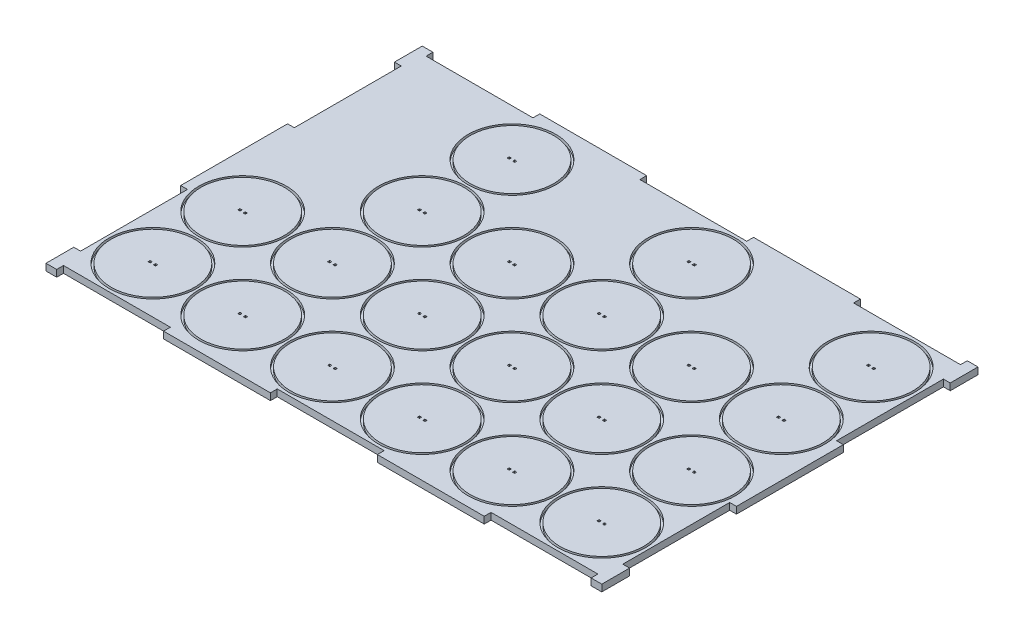
SolidWorks part; units mm, degrees
material "Oak"
ref_plane "Front Plane" through (0, 0, 0) normal (0, 0, 1) x (1, 0, 0)
ref_plane "Top Plane" through (0, 0, 0) normal (0, 1, 0) x (1, 0, 0)
ref_plane "Right Plane" through (0, 0, 0) normal (1, 0, 0) x (0, 0, -1)
sketch "Sketch2" plane through (0, 0, 0) normal (0, 1, 0) x (1, 0, 0)
  line L2 (105, -63) -> (63, -63) construction
  line L3 (105, -63) -> (-105, 63) construction
  line L4 (-105, -63) -> (-105, 63) construction
  line L5 (-105, 63) -> (105, 63) construction
  line L6 (-105, -63) -> (105, 63) construction
  circle A0 centre (105, -63) radius 20
  circle A1 centre (63, -63) radius 20
  circle A2 centre (21, -63) radius 20
  circle A3 centre (-21, -63) radius 20
  circle A4 centre (-63, -63) radius 20
  circle A5 centre (-105, -63) radius 20
  circle A6 centre (63, -21) radius 20
  circle A7 centre (21, -21) radius 20
  circle A8 centre (-21, -21) radius 20
  circle A9 centre (-63, -21) radius 20
  circle A10 centre (-105, -21) radius 20
  circle A11 centre (63, 21) radius 20
  circle A12 centre (21, 21) radius 20
  circle A13 centre (-21, 21) radius 20
  circle A14 centre (-63, 21) radius 20
  circle A17 centre (21, 63) radius 20
  circle A19 centre (-63, 63) radius 20
  circle A21 centre (105, -21) radius 20
  circle A22 centre (105, 21) radius 20
  circle A23 centre (105, 63) radius 20
  circle A24 centre (-105, 63) radius 20
  circle A25 centre (-105, 21) radius 20
  circle A26 centre (-21, 63) radius 20
  circle A27 centre (63, 63) radius 20
  point P0 (0, 0)
  dimension "D1" = 40
  dimension "D2" = 42
  dimension "D6" = 4
  dimension "D4" = 42
  dimension "D5" = 6
sketch "Sketch3" plane through (0, 0, 0) normal (0, 1, 0) x (1, 0, 0)
  line L1 (130, 88) -> (-130, 88)
  line L2 (130, 88) -> (130, -88)
  line L3 (130, -88) -> (-130, -88)
  line L4 (-130, 88) -> (-130, -88)
  line L5 (130, 88) -> (-130, -88) construction
  line L6 (130, -88) -> (-130, 88) construction
  circle A0 centre (-105, -63) radius 20 construction
  point P6 (0, 0)
  dimension "D1" = 25
  dimension "D2" = 25
extrude "Boss-Extrude2" add sketch "Sketch3" along normal mid plane 3.175
sketch "Sketch4" plane through (0, 1.5875, 0) normal (0, 1, 0) x (1, 0, 0)
  line L0 (105, -63) -> (63, -63) construction
  circle A25 centre (63, -63) radius 20.5
  circle A26 centre (105, -63) radius 20.5
  circle A27 centre (105, -63) radius 20.5
  circle A28 centre (105, -63) radius 19.5
  circle A29 centre (105, -63) radius 19.5
  circle A30 centre (63, -63) radius 19.5
  circle A31 centre (21, -63) radius 20.5
  circle A32 centre (21, -63) radius 19.5
  circle A33 centre (-21, -63) radius 20.5
  circle A34 centre (-21, -63) radius 19.5
  circle A35 centre (-63, -63) radius 20.5
  circle A36 centre (-63, -63) radius 19.5
  circle A37 centre (-105, -63) radius 20.5
  circle A38 centre (-105, -63) radius 19.5
  circle A39 centre (63, -21) radius 20.5
  circle A40 centre (63, -21) radius 19.5
  circle A41 centre (21, -21) radius 20.5
  circle A42 centre (21, -21) radius 19.5
  circle A43 centre (-21, -21) radius 20.5
  circle A44 centre (-21, -21) radius 19.5
  circle A45 centre (-63, -21) radius 20.5
  circle A46 centre (-63, -21) radius 19.5
  circle A47 centre (-105, -21) radius 20.5
  circle A48 centre (-105, -21) radius 19.5
  circle A49 centre (63, 21) radius 20.5
  circle A50 centre (63, 21) radius 19.5
  circle A51 centre (21, 21) radius 20.5
  circle A52 centre (21, 21) radius 19.5
  circle A53 centre (-21, 21) radius 20.5
  circle A54 centre (-21, 21) radius 19.5
  circle A55 centre (-63, 21) radius 20.5
  circle A56 centre (-63, 21) radius 19.5
  circle A61 centre (21, 63) radius 20.5
  circle A62 centre (21, 63) radius 19.5
  circle A65 centre (-63, 63) radius 20.5
  circle A66 centre (-63, 63) radius 19.5
  circle A69 centre (105, -21) radius 20.5
  circle A70 centre (105, -21) radius 19.5
  circle A71 centre (105, 21) radius 20.5
  circle A72 centre (105, 21) radius 19.5
  circle A73 centre (105, 63) radius 20.5
  circle A74 centre (105, 63) radius 19.5
  circle A75 centre (-105, 63) radius 20.5 [skipped]
  circle A76 centre (-105, 63) radius 19.5 [skipped]
  circle A77 centre (-105, 21) radius 19.5 [skipped]
  circle A78 centre (-105, 21) radius 20.5 [skipped]
  circle A79 centre (-21, 63) radius 20.5 [skipped]
  circle A80 centre (-21, 63) radius 19.5 [skipped]
  circle A81 centre (63, 63) radius 20.5 [skipped]
  circle A82 centre (63, 63) radius 19.5 [skipped]
  dimension "D3" = 42
  dimension "D1" = 0.5
  dimension "D2" = 0.5
  dimension "D4" = 6
  dimension "D5" = 4
extrude "Cut-Extrude1" cut sketch "Sketch4" against normal blind 1.5
sketch "Sketch5" plane through (0, 1.5875, 0) normal (0, 1, 0) x (1, 0, 0)
  line L0 (85, -63) -> (125, -63) construction
  line L1 (105, -58.1195) -> (105, -66.5107) construction
  line L2 (103.23, -62.5) -> (104.23, -62.5)
  line L3 (103.23, -62.5) -> (103.23, -63.5)
  line L4 (103.23, -63.5) -> (104.23, -63.5)
  line L5 (104.23, -62.5) -> (104.23, -63.5)
  line L6 (103.23, -62.5) -> (104.23, -63.5) construction
  line L7 (103.23, -63.5) -> (104.23, -62.5) construction
  line L8 (106.77, -63.5) -> (105.77, -62.5) construction
  line L9 (106.77, -62.5) -> (105.77, -63.5) construction
  line L10 (105.77, -62.5) -> (105.77, -63.5)
  line L11 (106.77, -63.5) -> (105.77, -63.5)
  line L12 (106.77, -62.5) -> (106.77, -63.5)
  line L13 (106.77, -62.5) -> (105.77, -62.5)
  circle A1 centre (-63, -63) radius 20
  circle A2 centre (-63, -63) radius 20
  circle A3 centre (-21, -63) radius 20
  circle A4 centre (-21, -63) radius 20
  circle A5 centre (21, -63) radius 20
  circle A6 centre (21, -63) radius 20
  circle A7 centre (63, -63) radius 20
  circle A8 centre (63, -63) radius 20
  circle A9 centre (105, -63) radius 20
  circle A10 centre (105, -63) radius 20
  circle A11 centre (21, 21) radius 20
  circle A12 centre (21, 21) radius 20
  circle A13 centre (63, 21) radius 20
  circle A14 centre (63, 21) radius 20
  circle A15 centre (-105, -21) radius 20
  circle A16 centre (-105, -21) radius 20
  circle A17 centre (-63, -21) radius 20
  circle A18 centre (-63, -21) radius 20
  circle A19 centre (-21, -21) radius 20
  circle A20 centre (-21, -21) radius 20
  circle A21 centre (21, -21) radius 20
  circle A22 centre (21, -21) radius 20
  circle A23 centre (63, -21) radius 20
  circle A24 centre (63, -21) radius 20
  circle A25 centre (-105, -63) radius 20
  circle A26 centre (-105, -63) radius 20
  circle A27 centre (-63, 63) radius 20
  circle A28 centre (-63, 63) radius 20
  circle A29 centre (21, 63) radius 20
  circle A30 centre (21, 63) radius 20
  circle A31 centre (-63, 21) radius 20
  circle A32 centre (-63, 21) radius 20
  circle A33 centre (-21, 21) radius 20
  circle A34 centre (-21, 21) radius 20
  circle A35 centre (105, 63) radius 20
  circle A36 centre (105, 63) radius 20
  circle A37 centre (105, 21) radius 20
  circle A38 centre (105, 21) radius 20
  circle A39 centre (105, -21) radius 20
  circle A40 centre (105, -21) radius 20
  point P62 (103.73, -63)
  point P73 (106.27, -63)
  dimension "D21" = 1.27
  dimension "D22" = 1
  dimension "D23" = 1
  dimension "D1" = 0
  dimension "D2" = 0
  dimension "D3" = 0
  dimension "D4" = 0
  dimension "D5" = 0
  dimension "D6" = 0
  dimension "D7" = 0
  dimension "D8" = 0
  dimension "D9" = 0
  dimension "D10" = 0
  dimension "D11" = 0
  dimension "D12" = 0
  dimension "D13" = 0
  dimension "D14" = 0
  dimension "D15" = 0
  dimension "D16" = 0
  dimension "D17" = 0
  dimension "D18" = 0
  dimension "D19" = 0
  dimension "D20" = 0
extrude "Cut-Extrude9" cut sketch "Sketch5" against normal blind 11.5 and the other way blind 11.5 contours L5 L2 L3 L4 | L12 L13 L10 L11 region at (103.73, 1.5875, 63) region at (106.27, 1.5875, 63)
pattern_linear "LPattern1" count 4 spacing 42 along (0, 0, -1) count 6 spacing 42 along (-1, 0, 0) skipping (2, 5), (3, 1), (3, 3), (3, 5) of "Cut-Extrude9"
sketch "Sketch9" plane through (0, 1.5875, 0) normal (0, 1, 0) x (1, 0, 0)
  line L0 (-130, 75) -> (-126.825, 75)
  line L1 (-130, 88) -> (-130, -88) construction
  line L2 (-126.825, 75) -> (-126.825, 25)
  line L3 (-130, -25) -> (-126.825, -25)
  line L4 (-126.825, -25) -> (-126.825, -75)
  line L5 (-126.825, -75) -> (-130, -75)
  line L6 (-130, 0) -> (130, 0) construction
  line L7 (-126.825, 25) -> (-130, 25)
  line L8 (130, 88) -> (-130, 88) construction
  line L9 (-130, -88) -> (130, -88) construction
  line L10 (0, 88) -> (0, -88) construction
  line L11 (126.825, 25) -> (130, 25)
  line L12 (126.825, -75) -> (130, -75)
  line L13 (126.825, -25) -> (126.825, -75)
  line L14 (130, -25) -> (126.825, -25)
  line L15 (126.825, 75) -> (126.825, 25)
  line L16 (130, 75) -> (126.825, 75)
  line L17 (-125, 88) -> (-125, 84.82)
  line L18 (-125, 84.82) -> (-75, 84.82)
  line L19 (-75, 84.82) -> (-75, 88)
  line L20 (-25, 88) -> (-25, 84.82)
  line L21 (-25, 84.82) -> (25, 84.82)
  line L22 (25, 84.82) -> (25, 88)
  line L23 (75, 88) -> (75, 84.82)
  line L24 (75, 84.82) -> (125, 84.82)
  line L25 (125, 84.82) -> (125, 88)
  line L26 (130, -88) -> (130, 88) construction
  line L27 (125, -84.82) -> (125, -88)
  line L28 (75, -84.82) -> (125, -84.82)
  line L29 (75, -88) -> (75, -84.82)
  line L30 (25, -84.82) -> (25, -88)
  line L31 (-25, -84.82) -> (25, -84.82)
  line L32 (-25, -88) -> (-25, -84.82)
  line L33 (-75, -84.82) -> (-75, -88)
  line L34 (-125, -84.82) -> (-75, -84.82)
  line L35 (-125, -88) -> (-125, -84.82)
  line M29 (-130, 88) -> (-130, -88)
  line M30 (-130, -88) -> (130, -88)
  line M31 (130, -88) -> (130, 88)
  line M32 (130, 88) -> (-130, 88)
  dimension "D1" = 50
  dimension "D2" = 50
  dimension "D3" = 13
  dimension "D4" = 50
  dimension "D5" = 13
  dimension "D6" = 5
  dimension "D7" = 50
  dimension "D8" = 3.175
  dimension "D9" = 3.18
  dimension "D10" = 50
  dimension "D11" = 50
  dimension "D12" = 50
  dimension "D13" = 50
  dimension "D14" = 5
ref_axis "Axis2" through (0, 2.0625, 0) along (0, -1, 0)
extrude "Cut-Extrude10" cut sketch "Sketch9" against normal blind 11.5 and the other way through all contours L35 L33 L34 M30 | L5 L4 L3 M29 | L32 L30 L31 M30 | L16 L15 L11 M31 | L24 L25 L23 M32 | L21 L22 L20 M32 | L7 L2 L0 M29 | L18 L19 L17 M32 | L29 L27 L28 M30 | L14 L13 L12 M31 region at (-128.4125, 1.5875, -50) region at (-100, 1.5875, -86.41) region at (-128.4125, 1.5875, 50) region at (0, 1.5875, -86.41) region at (-100, 1.5875, 86.41) region at (100, 1.5875, -86.41) region at (0, 1.5875, 86.41) region at (128.4125, 1.5875, -50) region at (100, 1.5875, 86.41) region at (128.4125, 1.5875, 50)
